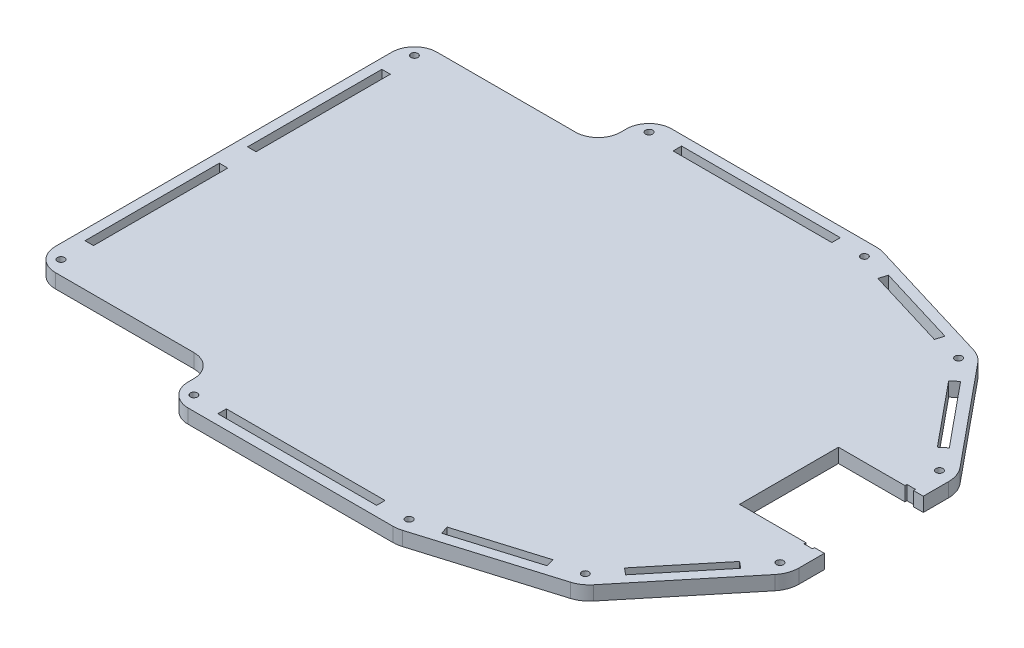
SolidWorks part; units mm, degrees
material "PVC rigido"
ref_plane "Piano frontale" through (0, 0, 0) normal (0, 0, 1) x (1, 0, 0)
ref_plane "Piano superiore" through (0, 0, 0) normal (0, 1, 0) x (1, 0, 0)
ref_plane "Piano destro" through (0, 0, 0) normal (1, 0, 0) x (0, 0, -1)
sketch "Schizzo1" plane through (0, 0, 0) normal (0, 1, 0) x (1, 0, 0)
  line L0 (65, 67.5) -> (65, 85.5)
  line L1 (0, 67.5) -> (65, 67.5)
  line L2 (0, 67.5) -> (0, -67.5)
  line L3 (0, -67.5) -> (65, -67.5)
  line L4 (65, 67.5) -> (65, -67.5) construction
  line L5 (65, 85.5) -> (146.8751, 85.5)
  line L6 (230, 30) -> (230, -30)
  line L7 (146.8751, -85.5) -> (65, -85.5)
  line L8 (65, -85.5) -> (65, -67.5)
  line L9 (230, 0) -> (65, 0) construction
  line L10 (230, 30) -> (196.8501, 70.3498)
  line L11 (196.8501, 70.3498) -> (146.8751, 85.5)
  line L12 (230, -30) -> (196.8501, -70.3498)
  line L13 (196.8501, -70.3498) -> (146.8751, -85.5)
  arc A0 (230, 30) -> (146.8751, 85.5) centre (146.8751, -4.5) ccw construction
  arc A1 (146.8751, -85.5) -> (230, -30) centre (146.8751, 4.5) ccw construction
  dimension "D5" = 60
  dimension "D6" = 90
  dimension "D1" = 135
  dimension "D2" = 65
  dimension "D3" = 165
  dimension "D4" = 18
extrude "Estrusione-Estrusione1" add sketch "Schizzo1" along normal blind 5
hole_wizard "Foro filettato M3x0.5-1" positions "Schizzo9" profile "Schizzo8" tap size "M3x0.5" standard "Ansi Metric"
sketch "Schizzo9" plane through (0, 5, 0) normal (0, 1, 0) x (1, 0, 0)
  line L102 (5, -62.5) -> (70, -62.5)
  line L103 (5, 62.5) -> (5, -62.5)
  line L104 (70, 62.5) -> (5, 62.5)
  line L105 (70, 80.5) -> (70, 62.5)
  line L106 (70, -62.5) -> (70, -80.5)
  line L107 (70, -80.5) -> (146.1339, -80.5)
  line L108 (146.1339, -80.5) -> (193.9489, -66.0046)
  line L109 (193.9489, -66.0046) -> (225, -28.2095)
  line L110 (225, -28.2095) -> (225, 28.2095)
  line L111 (225, 28.2095) -> (193.9489, 66.0046)
  line L112 (193.9489, 66.0046) -> (146.1339, 80.5)
  line L113 (146.1339, 80.5) -> (70, 80.5)
  line L114 (5, -62.5) -> (70, -62.5) construction
  line L115 (5, 62.5) -> (5, -62.5) construction
  line L116 (70, 62.5) -> (5, 62.5) construction
  line L117 (70, 80.5) -> (70, 62.5) construction
  line L118 (70, -62.5) -> (70, -80.5) construction
  line L119 (70, -80.5) -> (146.1339, -80.5) construction
  line L120 (146.1339, -80.5) -> (193.9489, -66.0046) construction
  line L121 (193.9489, -66.0046) -> (225, -28.2095) construction
  line L122 (225, -28.2095) -> (225, 28.2095) construction
  line L123 (225, 28.2095) -> (193.9489, 66.0046) construction
  line L124 (193.9489, 66.0046) -> (146.1339, 80.5) construction
  line L125 (146.1339, 80.5) -> (70, 80.5) construction
  point P0 (193.9489, 66.0046)
  point P2 (225, 28.2095)
  point P4 (225, -28.2095)
  point P6 (193.9489, -66.0046)
  point P8 (146.1339, -80.5)
  point P10 (146.1339, 80.5)
  point P12 (70, 80.5)
  point P14 (70, -80.5)
  point P16 (5, -62.5)
  point P18 (5, 62.5)
  dimension "D1" = 5
sketch "Schizzo8" plane through (193.9489, 5, -66.0046) normal (1, 0, 0) x (0, 0, 1)
  line L0 (0, 0) -> (0, 8.2511)
  line L1 (0, 8.2511) -> (1.25, 7.5)
  line L2 (1.25, 7.5) -> (1.25, 0)
  line L5 (1.25, 0) -> (0, 0)
  line L10 (0, 8.2511) -> (-1.25, 7.5) construction
  line L11 (0, -6.35) -> (0, 107.95) construction
  dimension "Tap Drill Dia." = 2.5
  dimension "Tap Drill Depth" = 7.5
  dimension "Drill Angle" = 118
cosmetic thread "Filettatura del foro1" parameters "D1"=5, "D2"=3
cosmetic thread "Filettatura del foro2" parameters "D1"=5, "D2"=3
cosmetic thread "Filettatura del foro3" parameters "D1"=5, "D2"=3
cosmetic thread "Filettatura del foro4" parameters "D1"=5, "D2"=3
cosmetic thread "Filettatura del foro5" parameters "D1"=5, "D2"=3
cosmetic thread "Filettatura del foro6" parameters "D1"=5, "D2"=3
cosmetic thread "Filettatura del foro7" parameters "D1"=5, "D2"=3
cosmetic thread "Filettatura del foro8" parameters "D1"=5, "D2"=3
cosmetic thread "Filettatura del foro9" parameters "D1"=5, "D2"=3
cosmetic thread "Filettatura del foro10" parameters "D1"=5, "D2"=3
sketch "Schizzo4" plane through (0, 5, 0) normal (0, 1, 0) x (1, 0, 0)
  line L0 (105.9375, -85.5) -> (105.9375, -82) construction
  line L1 (80, -82) -> (136.1339, -82)
  line L2 (80, -82) -> (80, -79)
  line L3 (80, -79) -> (136.1339, -79)
  line L4 (136.1339, -82) -> (136.1339, -79)
  line L5 (217.493, 34.984) -> (199.1379, 57.3257)
  line L6 (136.1339, -80.5) -> (146.1339, -80.5) construction
  line L7 (146.1339, -80.5) -> (155.7038, -77.5988) construction
  line L8 (155.7038, -77.5988) -> (184.379, -68.9058) construction
  line L9 (80, 82) -> (136.1339, 82)
  line L10 (80, 82) -> (80, 79)
  line L11 (80, 79) -> (136.1339, 79)
  line L12 (136.1339, 82) -> (136.1339, 79)
  line L13 (65, -85.5) -> (146.8751, -85.5) construction
  line L14 (80, -80.5) -> (70, -80.5) construction
  line L15 (199.1379, 57.3257) -> (201.4559, 59.2301)
  line L16 (105.9375, 85.5) -> (105.9375, 82) construction
  line L17 (146.8751, 85.5) -> (65, 85.5) construction
  line L18 (80, 80.5) -> (70, 80.5) construction
  line L19 (201.4559, 59.2301) -> (219.811, 36.8884)
  line L20 (184.379, -68.9058) -> (193.9489, -66.0046) construction
  line L21 (193.9489, -66.0046) -> (200.2969, -58.2779) construction
  line L22 (200.2969, -58.2779) -> (218.652, -35.9362) construction
  line L23 (218.652, -35.9362) -> (225, -28.2095) construction
  line L24 (225, -28.2095) -> (225, -18.2095) construction
  line L25 (225, -18.2095) -> (225, 18.2095) construction
  line L26 (225, 18.2095) -> (225, 28.2095) construction
  line L27 (225, 28.2095) -> (218.652, 35.9362) construction
  line L28 (218.652, 35.9362) -> (200.2969, 58.2779) construction
  line L29 (200.2969, 58.2779) -> (193.9489, 66.0046) construction
  line L30 (193.9489, 66.0046) -> (184.379, 68.9058) construction
  line L31 (184.379, 68.9058) -> (155.7038, 77.5988) construction
  line L32 (155.7038, 77.5988) -> (146.1339, 80.5) construction
  line L33 (146.1339, 80.5) -> (136.1339, 80.5) construction
  line L34 (184.8142, 70.3413) -> (156.139, 79.0343)
  line L35 (156.139, 79.0343) -> (155.2686, 76.1633)
  line L36 (155.2686, 76.1633) -> (183.9438, 67.4703)
  line L37 (183.9438, 67.4703) -> (184.8142, 70.3413)
  line L38 (196.8501, 70.3498) -> (146.8751, 85.5) construction
  line L39 (219.811, 36.8884) -> (217.493, 34.984)
  line L40 (155.2686, -76.1633) -> (183.9438, -67.4703)
  line L41 (183.9438, -67.4703) -> (184.8142, -70.3413)
  line L42 (184.8142, -70.3413) -> (156.139, -79.0343)
  line L43 (156.139, -79.0343) -> (155.2686, -76.1633)
  line L44 (199.1379, -57.3257) -> (217.493, -34.984)
  line L45 (217.493, -34.984) -> (219.811, -36.8884)
  line L46 (219.811, -36.8884) -> (201.4559, -59.2301)
  line L47 (201.4559, -59.2301) -> (199.1379, -57.3257)
  dimension "D1" = 10
  dimension "D2" = 3
extrude "Taglio-Estrusione2" cut sketch "Schizzo4" against normal blind 10
sketch "Schizzo7" plane through (0, 5, 0) normal (0, 1, 0) x (1, 0, 0)
  line L0 (5, -52.5) -> (5, -62.5) construction
  line L1 (3.5, 52.5) -> (6.5, 52.5)
  line L2 (3.5, 52.5) -> (3.5, 5)
  line L3 (3.5, 5) -> (6.5, 5)
  line L4 (6.5, 52.5) -> (6.5, 5)
  line L5 (6.5, -5) -> (3.5, -5)
  line L6 (6.5, -5) -> (6.5, -52.5)
  line L7 (6.5, -52.5) -> (3.5, -52.5)
  line L8 (3.5, -5) -> (3.5, -52.5)
  line L10 (5, 52.5) -> (5, 62.5) construction
  line L12 (5, -5) -> (5, 5) construction
  line L13 (5, 0) -> (0, 0) construction
  line L14 (0, 67.5) -> (0, -67.5) construction
  line L15 (80, -79) -> (80, -82) construction
  line L16 (80, -80.5) -> (70, -80.5) construction
  line L19 (3.5, -28.75) -> (0, -28.75) construction
  dimension "D2" = 10
extrude "Taglio-Estrusione5" cut sketch "Schizzo7" against normal blind 10
sketch "Schizzo6" [suppressed] plane through (0, 3, 0) normal (0, 1, 0) x (1, 0, 0)
  line L0 (65, 67.5) -> (0, 67.5) construction
  line L1 (0, -67.5) -> (55, -67.5)
  line L2 (0, -67.5) -> (0, 67.5)
  line L3 (0, 67.5) -> (55, 67.5)
  line L4 (55, -67.5) -> (55, 67.5)
  line L5 (65, 85.5) -> (65, 67.5) construction
  dimension "D1" = 10
extrude "Taglio-Estrusione4" [suppressed] cut sketch "Schizzo6" against normal blind 10
sketch "Schizzo2" plane through (0, 5, 0) normal (0, 1, 0) x (1, 0, 0)
  line L0 (230, 17.5) -> (200, 17.5)
  line L1 (230, -30) -> (230, 30) construction
  line L2 (200, 17.5) -> (200, -17.5)
  line L3 (200, -17.5) -> (230, -17.5)
  line L4 (200, 0) -> (230, 0) construction
  line L5 (230, -30) -> (230, -17.5) construction
  line L6 (230, 30) -> (230, 17.5) construction
  line L7 (230, -30) -> (230, 30) construction
  dimension "D1" = 30
  dimension "D2" = 35
extrude "Taglio-Estrusione1" cut sketch "Schizzo2" against normal through all and the other way through all
fillet "Raccordo1" radius 8 6 edges at (0, 2.5, 67.5) (0, 2.5, -67.5) (65, 2.5, -85.5) (65, 2.5, 85.5) (65, 2.5, 67.5) (65, 2.5, -67.5)
sketch "Schizzo10" [suppressed] plane through (0, 3, 0) normal (0, 1, 0) x (1, 0, 0)
  line L0 (219.811, 36.8884) -> (217.493, 34.984) construction
  line L1 (223.5, -18.2095) -> (226.5, -18.2095)
  line L2 (223.5, -18.2095) -> (223.5, 18.2095)
  line L3 (223.5, 18.2095) -> (226.5, 18.2095)
  line L4 (226.5, -18.2095) -> (226.5, 18.2095)
extrude "Taglio-Estrusione6" [suppressed] cut sketch "Schizzo10" against normal through all
sketch "Schizzo11" plane through (0, 5, 0) normal (0, 1, 0) x (1, 0, 0)
  line L0 (230, -17.5) -> (200, -17.5) construction
  line L1 (223.5, -18.2095) -> (226.5, -18.2095)
  line L2 (223.5, -18.2095) -> (223.5, -17.5)
  line L3 (223.5, -17.5) -> (226.5, -17.5)
  line L4 (226.5, -18.2095) -> (226.5, -17.5)
  line L5 (200, 17.5) -> (230, 17.5) construction
  line L6 (223.5, 17.5) -> (226.5, 17.5)
  line L7 (223.5, 17.5) -> (223.5, 18.2095)
  line L8 (223.5, 18.2095) -> (226.5, 18.2095)
  line L9 (226.5, 17.5) -> (226.5, 18.2095)
  line L10 (219.811, 36.8884) -> (217.493, 34.984) construction
  line L11 (217.493, -34.984) -> (219.811, -36.8884) construction
extrude "Taglio-Estrusione7" cut sketch "Schizzo11" against normal blind 5
fillet "Raccordo2" radius 10 6 edges at (146.8751, 2.5, -85.5) (196.8501, 2.5, -70.3498) (230, 2.5, -30) (230, 2.5, 30) (196.8501, 2.5, 70.3498) (146.8751, 2.5, 85.5)
